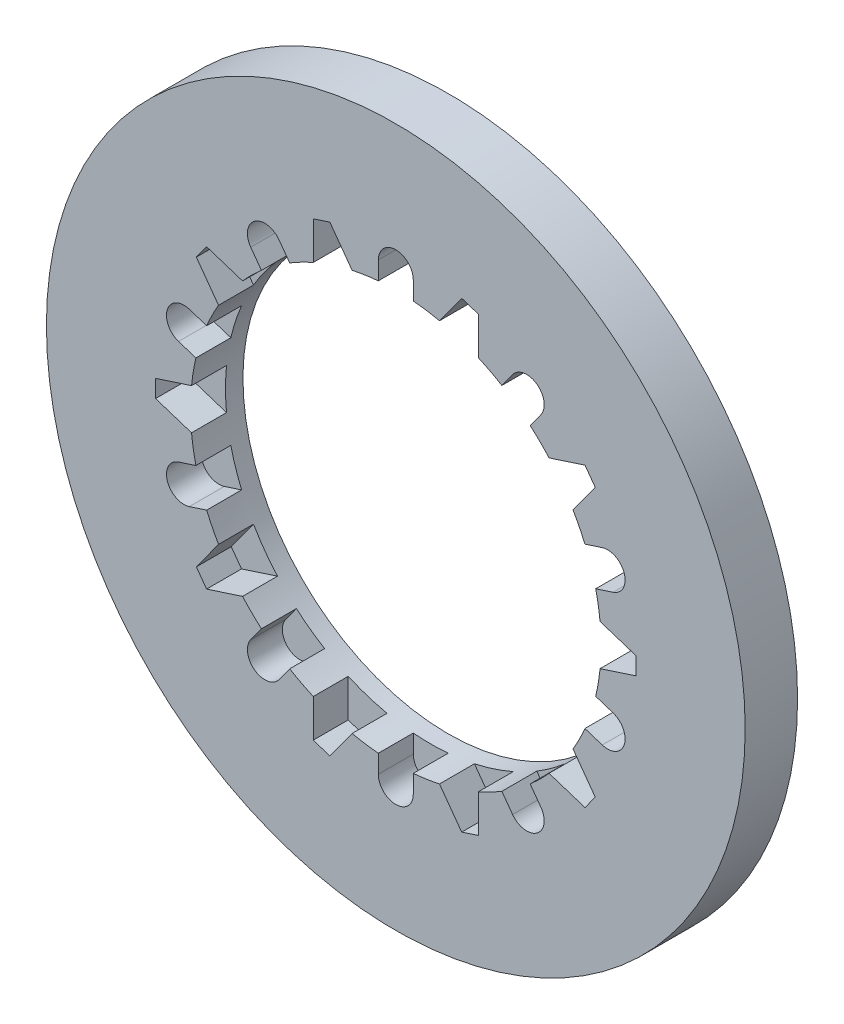
SolidWorks part; units mm, degrees
ref_plane "Front Plane" through (0, 0, 0) normal (0, 0, 1) x (1, 0, 0)
ref_plane "Top Plane" through (0, 0, 0) normal (0, 1, 0) x (1, 0, 0)
ref_plane "Right Plane" through (0, 0, 0) normal (1, 0, 0) x (0, 0, -1)
sketch "WheelAssemblyDimensions" plane through (0, 0, 0) normal (0, 0, 1) x (1, 0, 0)
  circle A0 centre (0, 0) radius 57.5 construction
  circle A1 centre (0, 0) radius 40 construction
  circle A2 centre (0, 0) radius 27.5 construction
  circle A3 centre (0, 0) radius 20 construction
  circle A4 centre (0, 0) radius 12.5 construction
  circle A5 centre (0, 0) radius 9.5 construction
  dimension "D1" = 115
  dimension "D2" = 80
  dimension "D3" = 55
  dimension "D4" = 40
  dimension "D5" = 25
  dimension "D6" = 19
sketch "Sketch2" plane through (0, 0, 0) normal (0, 0, 1) x (1, 0, 0)
  line L0 (0, 0) -> (0, 27.5) construction
  line L1 (0, 0) -> (-8.498, 26.1541) construction
  line L2 (-9.449, 25.845) -> (-7.5469, 26.4631)
  line L3 (-2, 25.5) -> (-2, 23.4147)
  line L4 (2, 25.5) -> (2, 23.4147)
  line L5 (-9.449, 25.845) -> (-9.449, 21.5166)
  line L6 (-7.5469, 26.4631) -> (-5.0027, 22.9613)
  line L7 (-5.0027, 22.9613) -> (-9.449, 21.5166) construction
  circle A0 centre (0, 0) radius 40
  circle A1 centre (0, 0) radius 23.5
  circle A2 centre (0, 25.5) radius 2
  circle A3 centre (0, 25.5) radius 1
  circle A4 centre (0, 0) radius 27.5 construction
  circle A5 centre (0, 0) radius 20
  dimension "D1" = 80
  dimension "D2" = 47
  dimension "D4" = 4
  dimension "D6" = 2
  dimension "D8" = 40
  dimension "D3" = 18
  dimension "D5" = 27.5
  dimension "D7" = 2
extrude "Boss-Extrude1" add sketch "Sketch2" along normal blind 4 contours A0 A2 L4 A1 L5 L2 L6 L3 | A1 L6 L2 L5 | A2 A3 | A2 L3 A1 | A3 | A2 A1 L4 region at (-7.7915, 23.9799, 0) region at (-1.55, 23.9174, 0) region at (1.55, 23.9174, 0) region at (0, 27.4434, 0) region at (-38.8686, 0, 0) region at (0, 25.5, 0)
extrude "Cut-Extrude2" cut sketch "Sketch2<3>" along normal blind 10 contours A1 L6 L2 L5 | A2 A3 | A3 | A2 L3 A1 | A2 A1 L4 region at (-7.7915, 23.9799, 0) region at (-1.55, 23.9174, 0) region at (1.55, 23.9174, 0) region at (0, 27.4434, 0) region at (0, 25.5, 0)
sketch "Sketch2<3>" plane through (0, 0, 0) normal (0, 0, 1) x (1, 0, 0) same geometry as "Sketch2"
ref_axis "Axis1" through (0, 0, 0) along (0, 0, 1)
pattern_circular "CirPattern1" count 10 over 360 about axis through (0, 0, 0) along (0, 0, 1) of "Cut-Extrude2"
extrude "Boss-Extrude2" add sketch "Sketch2<4>" against normal blind 2 contours A1 L6 L2 L5 | A2 A3 | A2 L3 A1 | A2 A1 L4 | A3 | A0 A2 L4 A1 L5 L2 L6 L3 region at (-7.7915, 23.9799, 0) region at (-1.55, 23.9174, 0) region at (1.55, 23.9174, 0) region at (0, 27.4434, 0) region at (-38.8686, 0, 0) region at (0, 25.5, 0)
sketch "Sketch2<4>" plane through (0, 0, 0) normal (0, 0, 1) x (1, 0, 0) same geometry as "Sketch2"
equation "\"tyre_ID\"= 115mm"
equation "\"disc_OD\" = 80mm"
equation "\"discbell_OD\" = 55mm"
equation "\"hub_OD\" = 40"
equation "\"bearing_ID\" = 25mm"
equation "\"shaft_OD\"= 19mm"
equation "\"D1@WheelAssemblyDimensions\" = \"tyre_ID\""
equation "\"D2@WheelAssemblyDimensions\" = \"disc_OD\""
equation "\"D3@WheelAssemblyDimensions\" = \"discbell_OD\""
equation "\"D4@WheelAssemblyDimensions\" = \"hub_OD\""
equation "\"D5@WheelAssemblyDimensions\" = \"bearing_ID\""
equation "\"D6@WheelAssemblyDimensions\" = \"shaft_OD\""
equation "\"D1@Sketch2\"=\"disc_OD\""
equation "\"D2@Sketch2\"=\"discbell_OD\"-8"
equation "\"D5@Sketch2\"=\"discbell_OD\"/2"
equation "\"D8@Sketch2\"=\"hub_OD\""
